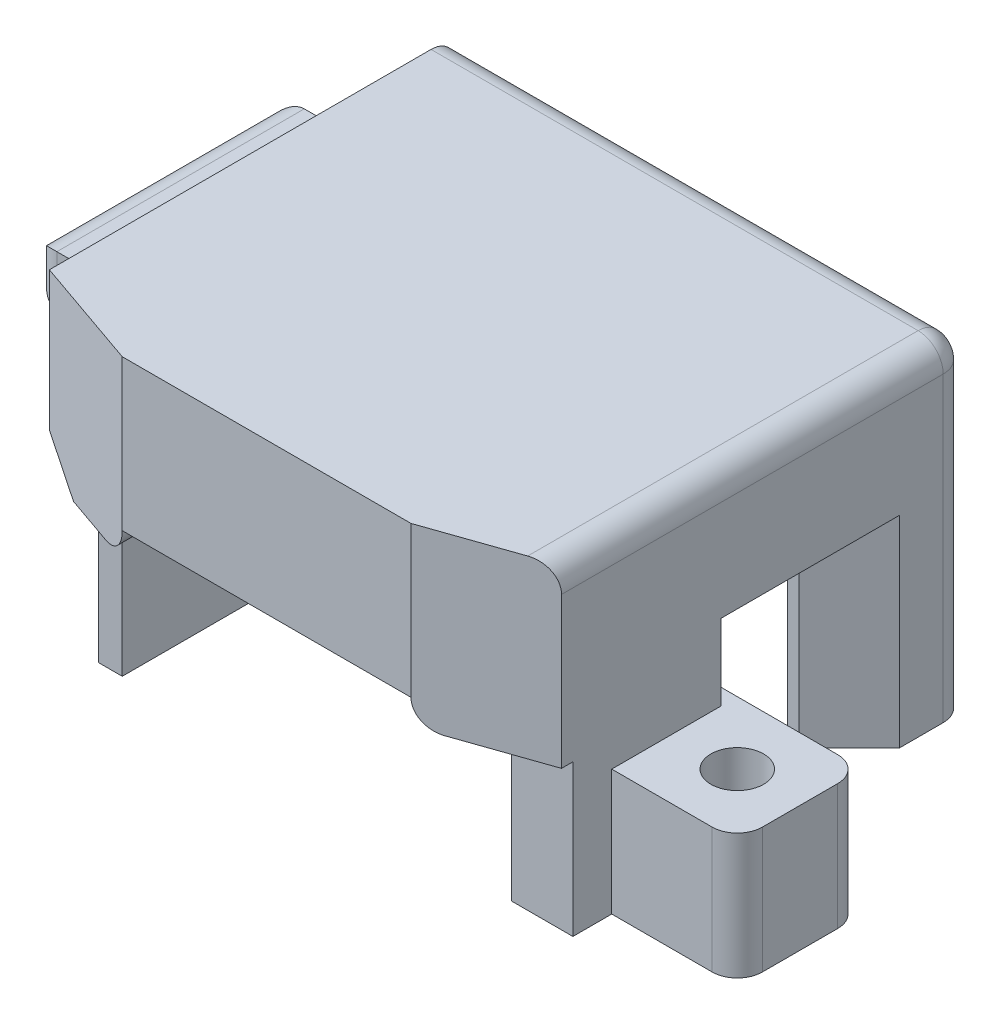
SolidWorks part; units mm, degrees
ref_plane "Front Plane" through (0, 0, 0) normal (0, 0, 1) x (1, 0, 0)
ref_plane "Top Plane" through (0, 0, 0) normal (0, 1, 0) x (1, 0, 0)
ref_plane "Right Plane" through (0, 0, 0) normal (1, 0, 0) x (0, 0, -1)
sketch "Sketch1" plane through (0, 0, 0) normal (0, 1, 0) x (1, 0, 0)
  line L1 (-22.86, -21.59) -> (22.86, -21.59)
  line L2 (-22.86, -21.59) -> (-22.86, 21.59)
  line L3 (-22.86, 21.59) -> (22.86, 21.59)
  line L4 (22.86, -21.59) -> (22.86, 21.59)
  line L5 (-22.86, -21.59) -> (22.86, 21.59) construction
  line L6 (-22.86, 21.59) -> (22.86, -21.59) construction
  point P0 (0, 0)
  dimension "D1" = 45.72
  dimension "D2" = 43.18
extrude "Boss-Extrude1" add sketch "Sketch1" along normal blind 31.75 contours L2 L1 L4 L3
sketch "Sketch2" plane through (0, 31.75, 0) normal (0, 1, 0) x (1, 0, 0)
  line L1 (-19.685, -18.415) -> (19.685, -18.415)
  line L2 (-19.685, -18.415) -> (-19.685, 18.415)
  line L3 (-19.685, 18.415) -> (19.685, 18.415)
  line L4 (19.685, -18.415) -> (19.685, 18.415)
  line L5 (-19.685, -18.415) -> (19.685, 18.415) construction
  line L6 (-19.685, 18.415) -> (19.685, -18.415) construction
  point P0 (0, 0)
  dimension "D1" = 39.37
  dimension "D2" = 36.83
extrude "Cut-Extrude3" cut sketch "Sketch2" against normal blind 25.4
sketch "Sketch3" plane through (0, 0, 21.59) normal (0, 0, 1) x (1, 0, 0)
  line L1 (-22.86, 31.75) -> (22.86, 31.75)
  line L2 (-22.86, 31.75) -> (-22.86, 0)
  line L3 (-22.86, 0) -> (22.86, 0)
  line L4 (22.86, 31.75) -> (22.86, 0)
extrude "Cut-Extrude5" cut sketch "Sketch3" against normal blind 3.175
sketch "Sketch6" plane through (0, 31.75, 0) normal (0, 1, 0) x (1, 0, 0)
  line L1 (-19.685, -18.415) -> (-22.86, -18.415)
  line L2 (-19.685, -18.415) -> (-19.685, 21.59)
  line L3 (-19.685, 21.59) -> (-22.86, 21.59)
  line L4 (-22.86, -18.415) -> (-22.86, 21.59)
  line L5 (19.685, -18.415) -> (22.86, -18.415)
  line L6 (19.685, -18.415) -> (19.685, 21.59)
  line L7 (19.685, 21.59) -> (22.86, 21.59)
  line L8 (22.86, -18.415) -> (22.86, 21.59)
  line L9 (-19.685, 18.415) -> (19.685, 18.415)
  line L10 (-19.685, 18.415) -> (-19.685, 21.59)
  line L11 (-19.685, 21.59) -> (19.685, 21.59)
  line L12 (19.685, 18.415) -> (19.685, 21.59)
  line M4 (-19.685, 18.415) -> (19.685, 18.415)
  line M5 (19.685, 18.415) -> (19.685, -18.415)
  line M6 (19.685, -18.415) -> (22.86, -18.415)
  line M7 (22.86, -18.415) -> (22.86, 21.59)
  line M8 (22.86, 21.59) -> (-22.86, 21.59)
extrude "Boss-Extrude4" add sketch "Sketch6" along normal up to vertex (38.1 mm away) contours L6 M5 M6 M7 M8 | L6 L2 M4 M8
sketch "Sketch7" plane through (0, 0, -18.415) normal (0, 0, 1) x (1, 0, 0)
  line L0 (19.685, 6.35) -> (19.685, 69.85) construction
  line L1 (-19.685, 69.85) -> (19.685, 69.85)
  line L2 (-19.685, 69.85) -> (-19.685, 44.6984)
  line L3 (-19.685, 44.6984) -> (19.685, 44.6984)
  line L4 (19.685, 69.85) -> (19.685, 44.6984)
extrude "Boss-Extrude5" add sketch "Sketch7" along normal up to vertex (36.83 mm away)
sketch "Sketch8" plane through (22.86, 0, 0) normal (1, 0, 0) x (0, 0, -1)
  line L1 (-18.415, 69.85) -> (21.59, 69.85)
  line L2 (-18.415, 69.85) -> (-18.415, 0)
  line L3 (-18.415, 0) -> (21.59, 0)
  line L4 (21.59, 69.85) -> (21.59, 0)
extrude "Boss-Extrude6" add sketch "Sketch8" along normal blind 6.35
sketch "Sketch9" plane through (-22.86, 0, 0) normal (-1, 0, 0) x (0, 0, 1)
  line L1 (18.415, 69.85) -> (-21.59, 69.85)
  line L2 (18.415, 69.85) -> (18.415, 0)
  line L3 (18.415, 0) -> (-21.59, 0)
  line L4 (-21.59, 69.85) -> (-21.59, 0)
extrude "Boss-Extrude7" add sketch "Sketch9" along normal blind 6.35
sketch "Sketch11" plane through (-29.21, 0, 0) normal (-1, 0, 0) x (0, 0, 1)
  line L0 (-1.5875, 69.85) -> (-1.5875, 58.2804)
  line L1 (18.415, 69.85) -> (-21.59, 69.85) construction
  line L2 (-1.5875, 58.2804) -> (-7.9375, 58.2804)
  line L4 (-7.9375, 58.2804) -> (4.7625, 58.2804)
  line L5 (-7.9375, 58.2804) -> (-7.9375, 44.3104)
  line L6 (-7.9375, 44.3104) -> (4.7625, 44.3104)
  line L7 (4.7625, 58.2804) -> (4.7625, 44.3104)
  dimension "D1" = 13.97
  dimension "D2" = 12.7
  dimension "D3" = 6.35
extrude "Cut-Extrude8" cut sketch "Sketch11" against normal blind 61.468 contours L7 L4 L2 L5 L6
sketch "Sketch12" plane through (-29.21, 0, 0) normal (-1, 0, 0) x (0, 0, 1)
  line L0 (4.7625, 58.2804) -> (4.7625, 69.85)
  line L1 (18.415, 69.85) -> (-21.59, 69.85) construction
sketch "Sketch13" plane through (0, 69.85, 0) normal (0, 1, 0) x (1, 0, 0)
  line L0 (-29.21, -4.7625) -> (29.21, -4.7625)
  line L1 (29.21, 21.59) -> (29.21, -18.415) construction
  line L3 (-29.21, -4.7625) -> (29.21, -4.7625)
  line L4 (-29.21, -4.7625) -> (-29.21, 21.59)
  line L5 (-29.21, 21.59) -> (29.21, 21.59)
  line L6 (29.21, -4.7625) -> (29.21, 21.59)
extrude "Boss-Extrude8" add sketch "Sketch13" along normal blind 16.002
sketch "Sketch14" plane through (0, 0, -21.59) normal (0, 0, -1) x (-1, 0, 0)
  line L0 (10.16, 85.852) -> (29.21, 85.852)
  line L1 (-29.21, 85.852) -> (29.21, 85.852) construction
  line L2 (0, 85.852) -> (-10.16, 85.852)
  line L3 (-10.16, 85.852) -> (-10.16, 73.1756)
  line L4 (-10.16, 73.1756) -> (-3.81, 73.1756)
  line L5 (-3.81, 73.1756) -> (10.16, 73.1756)
  line L6 (10.16, 73.1756) -> (10.16, 85.852)
  line L7 (10.16, 85.852) -> (0, 85.852)
  line L8 (-10.16, 73.1756) -> (10.16, 73.1756)
  line L9 (-29.21, 85.852) -> (-10.16, 85.852)
  line M3 (29.21, 85.852) -> (-29.21, 85.852)
extrude "Cut-Extrude9" cut sketch "Sketch14" against normal blind 16.51 contours L5 L6 L3 L4 M3
sketch "Sketch15" plane through (0, 0, 4.7625) normal (0, 0, 1) x (1, 0, 0)
  line L0 (-29.21, 85.852) -> (-18.8998, 85.852)
  line L1 (-29.21, 85.852) -> (29.21, 85.852) construction
  line L2 (29.21, 85.852) -> (19.0951, 85.852)
  line L3 (-29.21, 69.85) -> (29.21, 69.85) construction
  line L4 (-18.8998, 85.852) -> (19.0951, 85.852)
  line L5 (-18.8998, 85.852) -> (-18.8998, 69.85)
  line L6 (-18.8998, 69.85) -> (19.0951, 69.85)
  line L7 (19.0951, 85.852) -> (19.0951, 69.85)
extrude "Boss-Extrude9" add sketch "Sketch15" along normal blind 5.08 contours L5 L4 L7 L6
sketch "Sketch16" plane through (0, 0, 0) normal (0, -1, 0) x (1, 0, 0)
  line L1 (-29.21, 18.415) -> (29.21, 18.415)
  line L2 (-29.21, 18.415) -> (-29.21, -21.59)
  line L3 (-29.21, -21.59) -> (29.21, -21.59)
  line L4 (29.21, 18.415) -> (29.21, -21.59)
extrude "Cut-Extrude11" cut sketch "Sketch16" against normal blind 38.1
sketch "Sketch17" plane through (0, 44.3104, 0) normal (0, 1, 0) x (1, 0, 0)
  line L1 (29.21, 7.9375) -> (19.685, 7.9375)
  line L2 (29.21, 7.9375) -> (29.21, -4.7625)
  line L3 (29.21, -4.7625) -> (19.685, -4.7625)
  line L4 (19.685, 7.9375) -> (19.685, -4.7625)
extrude "Boss-Extrude10" add sketch "Sketch17" along normal up to vertex (13.97 mm away)
sketch "Sketch18" plane through (0, 44.3104, 0) normal (0, 1, 0) x (1, 0, 0)
  line L1 (-29.21, 7.9375) -> (-19.685, 7.9375)
  line L2 (-29.21, 7.9375) -> (-29.21, -4.7625)
  line L3 (-29.21, -4.7625) -> (-19.685, -4.7625)
  line L4 (-19.685, 7.9375) -> (-19.685, -4.7625)
extrude "Boss-Extrude11" add sketch "Sketch18" along normal up to vertex (13.97 mm away)
sketch "Sketch19" plane through (0, 0, 18.415) normal (0, 0, 1) x (1, 0, 0)
  line L6 (19.685, 44.6984) -> (-19.685, 44.6984)
  line L7 (19.685, 44.6984) -> (19.685, 48.5084)
  line L8 (19.685, 48.5084) -> (-19.685, 48.5084)
  line L9 (-19.685, 44.6984) -> (-19.685, 48.5084)
  dimension "D1" = 3.81
extrude "Boss-Extrude14" add sketch "Sketch19" along normal blind 5.08
sketch "Sketch21" plane through (0, 44.6984, 0) normal (0, -1, 0) x (1, 0, 0)
  line L0 (-19.685, 18.415) -> (-19.685, 23.495)
  line L1 (-19.685, 23.495) -> (-14.605, 23.495)
  line L2 (-19.685, 23.495) -> (19.685, 23.495) construction
  line L3 (-14.605, 23.495) -> (-19.685, 18.415)
  line L4 (19.685, 18.415) -> (19.685, 23.495)
  line L5 (19.685, 23.495) -> (14.605, 23.495)
  line L6 (14.605, 23.495) -> (19.685, 18.415)
  dimension "D1" = 5.08
  dimension "D2" = 5.08
extrude "Cut-Extrude12" cut sketch "Sketch21" against normal up to vertex (3.81 mm away) contours L6 L4 L5 | L3 L0 L1
sketch "Sketch34" plane through (0, 44.6984, 0) normal (0, -1, 0) x (-1, 0, 0)
  line L0 (14.605, -23.495) -> (19.685, -18.415)
  line L1 (19.685, -18.415) -> (14.605, -18.415)
  line L2 (14.605, -18.415) -> (14.605, -23.495)
sketch "Sketch35" plane through (0, 0, 18.415) normal (0, 0, 1) x (1, 0, 0)
  line L0 (19.685, 44.6984) -> (29.21, 44.6984)
  line L1 (29.21, 69.85) -> (29.21, 38.1) construction
  line L2 (-19.685, 44.6984) -> (-29.21, 44.6984)
  line L3 (-29.21, 38.1) -> (-29.21, 69.85) construction
sketch "Sketch36" plane through (0, 44.6984, 0) normal (0, -1, 0) x (1, 0, 0)
  line L0 (-14.605, 23.495) -> (-29.21, 18.415)
  line L1 (-19.685, 18.415) -> (-29.21, 18.415) construction
  line L2 (-29.21, 18.415) -> (-14.605, 18.415)
  line L3 (-14.605, 18.415) -> (-14.605, 23.495)
  line L4 (14.605, 23.495) -> (29.21, 18.415)
  line L5 (29.21, 18.415) -> (14.605, 18.415)
  line L6 (14.605, 18.415) -> (14.605, 23.495)
extrude "Boss-Extrude22" add sketch "Sketch36" against normal up to vertex (3.81 mm away) up to point (-14.605, 48.5084, 23.495)
sketch "Sketch37" plane through (0, 48.5084, 0) normal (0, 1, 0) x (1, 0, 0)
  line L0 (-29.21, -18.415) -> (-14.605, -23.495)
  line L1 (-14.605, -23.495) -> (14.605, -23.495)
  line L2 (14.605, -23.495) -> (29.21, -18.415)
  line L3 (29.21, -18.415) -> (-29.21, -18.415)
extrude "Boss-Extrude23" add sketch "Sketch37" along normal up to vertex
sketch "Sketch39" plane through (0, 44.6984, 0) normal (0, -1, 0) x (1, 0, 0)
  line L0 (-29.21, 18.415) -> (-14.605, 23.495)
  line L1 (-14.605, 23.495) -> (14.605, 23.495)
  line L2 (14.605, 23.495) -> (29.21, 18.415)
  line L3 (29.21, 18.415) -> (-29.21, 18.415)
extrude "Boss-Extrude24" add sketch "Sketch39" along normal up to vertex (6.5984 mm away)
sketch "Sketch40" plane through (0, 38.1, 0) normal (0, -1, 0) x (-1, 0, 0)
  line L0 (-29.21, 21.59) -> (29.21, 21.59)
  line L1 (29.21, 21.59) -> (29.21, -18.415)
  line L2 (29.21, -18.415) -> (14.605, -23.495)
  line L3 (14.605, -23.495) -> (-14.605, -23.495)
  line L4 (-14.605, -23.495) -> (-29.21, -18.415)
  line L5 (-29.21, -18.415) -> (-29.21, 21.59)
  line L6 (-19.685, 18.415) -> (-19.685, -18.415)
  line L7 (-19.685, -18.415) -> (19.685, -18.415)
  line L8 (19.685, -18.415) -> (19.685, 18.415)
  line L9 (19.685, 18.415) -> (-19.685, 18.415)
  line L10 (8.618, -12.0581) -> (8.725, -12.0414)
  line M7 (19.685, -18.415) -> (-19.685, -18.415)
  line M8 (-19.685, -18.415) -> (-19.685, 18.415)
  line M9 (-19.685, 18.415) -> (19.685, 18.415)
  line M10 (19.685, 18.415) -> (19.685, -18.415)
  line M11 (-29.21, 21.59) -> (-29.21, -18.415)
  line M12 (-29.21, -18.415) -> (-14.605, -23.495)
  line M13 (-14.605, -23.495) -> (14.605, -23.495)
  line M14 (14.605, -23.495) -> (29.21, -18.415)
  line M15 (29.21, -18.415) -> (29.21, 21.59)
  line M16 (29.21, 21.59) -> (-29.21, 21.59)
extrude "Boss-Extrude25" add sketch "Sketch40" along normal blind 4.826 contours M16 M11 M12 M13 M14 M15 M10 M7 M8 M9
sketch "Sketch42" plane through (0, 0, 9.8425) normal (0, 0, 1) x (1, 0, 0)
  line L1 (-18.8998, 85.852) -> (19.0951, 85.852)
  line L2 (-18.8998, 85.852) -> (-18.8998, 69.85)
  line L3 (-18.8998, 69.85) -> (19.0951, 69.85)
  line L4 (19.0951, 85.852) -> (19.0951, 69.85)
extrude "Boss-Extrude26" add sketch "Sketch42" along normal blind 3.302
sketch "Sketch43" plane through (0, 0, 4.7625) normal (0, 0, -1) x (-1, 0, 0)
  line L1 (19.685, 58.2804) -> (-19.685, 58.2804)
  line L2 (19.685, 58.2804) -> (19.685, 44.6984)
  line L3 (19.685, 44.6984) -> (-19.685, 44.6984)
  line L4 (-19.685, 58.2804) -> (-19.685, 44.6984)
extrude "Cut-Extrude13" cut sketch "Sketch43" against normal blind 6.35
sketch "Sketch45" plane through (0, 0, -7.9375) normal (0, 0, 1) x (1, 0, 0)
  line L1 (-19.685, 58.2804) -> (19.685, 58.2804)
  line L2 (-19.685, 58.2804) -> (-19.685, 44.6984)
  line L3 (-19.685, 44.6984) -> (19.685, 44.6984)
  line L4 (19.685, 58.2804) -> (19.685, 44.6984)
extrude "Boss-Extrude27" add sketch "Sketch45" along normal up to vertex
sketch "Sketch46" plane through (-29.21, 0, 0) normal (-1, 0, 0) x (0, 0, 1)
  line L0 (-21.59, 85.852) -> (-21.59, 33.274)
  line L1 (-21.59, 33.274) -> (18.415, 33.274)
  line L2 (18.415, 33.274) -> (18.415, 69.85)
  line L3 (18.415, 69.85) -> (13.1445, 69.85)
  line L4 (13.1445, 69.85) -> (13.1445, 85.852)
  line L5 (13.1445, 85.852) -> (-21.59, 85.852)
extrude "Cut-Extrude15" cut sketch "Sketch46" against normal blind 3.302
sketch "Sketch47" plane through (29.21, 0, 0) normal (1, 0, 0) x (0, 0, -1)
  line L0 (-4.7625, 85.852) -> (-4.7625, 69.85)
  line L1 (-4.7625, 69.85) -> (-18.415, 69.85)
  line L2 (-18.415, 69.85) -> (-18.415, 33.274)
  line L3 (-18.415, 33.274) -> (21.59, 33.274)
  line L4 (21.59, 33.274) -> (21.59, 85.852)
  line L5 (21.59, 33.274) -> (21.59, 85.852) construction
  line L6 (21.59, 85.852) -> (-4.7625, 85.852)
extrude "Cut-Extrude16" cut sketch "Sketch47" against normal blind 3.302
sketch "Sketch48" plane through (0, 0, 18.415) normal (0, 0, -1) x (-1, 0, 0)
  line L1 (-29.21, 69.85) -> (-25.908, 69.85)
  line L2 (-29.21, 69.85) -> (-29.21, 33.274)
  line L3 (-29.21, 33.274) -> (-25.908, 33.274)
  line L4 (-25.908, 69.85) -> (-25.908, 33.274)
extrude "Cut-Extrude17" cut sketch "Sketch48" against normal blind 3.302
sketch "Sketch49" plane through (0, 0, 18.415) normal (0, 0, -1) x (-1, 0, 0)
  line L1 (29.21, 69.85) -> (25.908, 69.85)
  line L2 (29.21, 69.85) -> (29.21, 33.274)
  line L3 (29.21, 33.274) -> (25.908, 33.274)
  line L4 (25.908, 69.85) -> (25.908, 33.274)
extrude "Cut-Extrude18" cut sketch "Sketch49" against normal blind 3.302
sketch "Sketch50" plane through (0, 85.852, 0) normal (0, 1, 0) x (1, 0, 0)
  line L1 (-25.908, 21.59) -> (37.3188, 21.59)
  line L2 (-25.908, 21.59) -> (-25.908, -24.3963)
  line L3 (-25.908, -24.3963) -> (37.3188, -24.3963)
  line L4 (37.3188, 21.59) -> (37.3188, -24.3963)
extrude "Cut-Extrude19" cut sketch "Sketch50" against normal up to vertex (16.002 mm away)
sketch "Sketch51" plane through (0, 69.85, 0) normal (0, 1, 0) x (1, 0, 0)
  line L1 (-25.908, 21.59) -> (29.0656, 21.59)
  line L2 (-25.908, 21.59) -> (-25.908, -24.9944)
  line L3 (-25.908, -24.9944) -> (29.0656, -24.9944)
  line L4 (29.0656, 21.59) -> (29.0656, -24.9944)
extrude "Cut-Extrude20" cut sketch "Sketch51" against normal blind 18.796
sketch "Sketch52" plane through (0, 33.274, 0) normal (0, -1, 0) x (-1, 0, 0)
  line L0 (-25.908, -19.5635) -> (-25.908, 21.59) construction
  line L1 (-19.685, -18.415) -> (-25.908, -18.415)
  line L2 (-19.685, -18.415) -> (-19.685, 1.6404)
  line L3 (-19.685, 1.6404) -> (-25.908, 1.6404)
  line L4 (-25.908, -18.415) -> (-25.908, 1.6404)
  line L6 (-25.908, 9.525) -> (-19.685, 9.525)
  line L7 (-25.908, 9.525) -> (-25.908, 18.415)
  line L8 (-25.908, 18.415) -> (-19.685, 18.415)
  line L9 (-19.685, 9.525) -> (-19.685, 18.415)
  line L10 (19.685, -18.415) -> (25.908, -18.415)
  line L11 (19.685, -18.415) -> (19.685, 21.59)
  line L12 (19.685, 21.59) -> (25.908, 21.59)
  line L13 (25.908, -18.415) -> (25.908, 21.59)
  line L14 (-25.908, 21.59) -> (19.685, 21.59)
  line L15 (-25.908, 21.59) -> (-25.908, 18.415)
  line L16 (-25.908, 18.415) -> (19.685, 18.415)
  line L17 (19.685, 21.59) -> (19.685, 18.415)
  line M2 (25.908, -19.5635) -> (25.908, 21.59)
  line M3 (25.908, 21.59) -> (-25.908, 21.59)
  line M4 (-25.908, 21.59) -> (-25.908, -19.5635)
  line M7 (19.685, 18.415) -> (19.685, -18.415)
  line M9 (-19.685, -18.415) -> (-19.685, 18.415)
  line M10 (-19.685, 18.415) -> (19.685, 18.415)
  dimension "D1" = 8.89
extrude "Boss-Extrude28" add sketch "Sketch52" along normal blind 15.3035 contours L3 L1 M9 M4 | L8 L6 M4 M9 | L11 L8 M10 M3 M4 | L11 L10 M7 M2 M3
sketch "Sketch53" plane through (25.908, 0, 0) normal (1, 0, 0) x (0, 0, -1)
  line L1 (-18.415, 17.9705) -> (-5.715, 17.9705)
  line L2 (-18.415, 17.9705) -> (-18.415, 21.7805)
  line L3 (-18.415, 21.7805) -> (-5.715, 21.7805)
  line L4 (-5.715, 17.9705) -> (-5.715, 21.7805)
  dimension "D1" = 12.7
  dimension "D2" = 3.81
sketch "Sketch54" plane through (-25.908, 0, 0) normal (-1, 0, 0) x (0, 0, 1)
  line L1 (18.415, 17.9705) -> (5.715, 17.9705)
  line L2 (18.415, 17.9705) -> (18.415, 21.7805)
  line L3 (18.415, 21.7805) -> (5.715, 21.7805)
  line L4 (5.715, 17.9705) -> (5.715, 21.7805)
extrude "Boss-Extrude29" add sketch "Sketch53" along normal blind 10.16
extrude "Boss-Extrude30" add sketch "Sketch54" along normal blind 10.16
sketch "Sketch55" plane through (0, 21.7805, 0) normal (0, 1, 0) x (1, 0, 0)
  line L0 (36.068, -18.415) -> (25.908, -18.415) construction
  line L1 (36.068, -5.715) -> (36.068, -18.415) construction
  line L2 (30.988, -18.415) -> (36.068, -18.415)
  line L3 (36.068, -18.415) -> (36.068, -12.065)
  arc A0 (30.988, -18.415) -> (36.068, -12.065) centre (30.353, -12.7) ccw
  line M2 (25.908, -18.415) -> (36.068, -18.415)
  line M3 (36.068, -18.415) -> (36.068, -5.715)
extrude "Cut-Extrude21" cut sketch "Sketch55" against normal blind 12.7 contours A0 M2 M3
sketch "Sketch56" plane through (0, 21.7805, 0) normal (0, 1, 0) x (1, 0, 0)
  line L0 (-36.068, -18.415) -> (-25.908, -18.415) construction
  line L1 (-36.068, -18.415) -> (-36.068, -5.715) construction
  line L2 (-30.988, -18.415) -> (-36.068, -18.415)
  line L3 (-36.068, -18.415) -> (-36.068, -12.065)
  arc A0 (-30.988, -18.415) -> (-36.068, -12.065) centre (-30.353, -12.7) cw
  line M4 (-36.068, -18.415) -> (-25.908, -18.415)
extrude "Cut-Extrude22" cut sketch "Sketch56" against normal blind 12.7 contours A0 L3 M4
sketch "Sketch60" plane through (0, 21.7805, 0) normal (0, 1, 0) x (1, 0, 0)
  circle A0 centre (30.353, -12.7) radius 2.667
  circle A1 centre (-30.353, -12.7) radius 2.667
extrude "Cut-Extrude25" cut sketch "Sketch60" against normal blind 10.16
sketch "Sketch62" plane through (0, 33.274, 0) normal (0, -1, 0) x (1, 0, 0)
  line L0 (-19.685, 18.415) -> (19.685, 18.415) construction
  line L1 (-14.605, 23.495) -> (14.605, 23.495)
  line L2 (-14.605, 23.495) -> (-14.605, 18.415)
  line L3 (-14.605, 18.415) -> (14.605, 18.415)
  line L4 (14.605, 23.495) -> (14.605, 18.415)
extrude "Cut-Extrude27" cut sketch "Sketch62" against normal blind 2.54
sketch "Sketch63" plane through (0, 0, -18.415) normal (0, 0, 1) x (1, 0, 0)
  line L0 (19.685, 17.9705) -> (-19.685, 17.9705) construction
  line L1 (-12.7, -1.0795) -> (12.7, -1.0795)
  line L2 (-12.7, -1.0795) -> (-12.7, 37.0205)
  line L3 (-12.7, 37.0205) -> (12.7, 37.0205)
  line L4 (12.7, -1.0795) -> (12.7, 37.0205)
  line L5 (-12.7, -1.0795) -> (12.7, 37.0205) construction
  line L6 (-12.7, 37.0205) -> (12.7, -1.0795) construction
  point P0 (0, 17.9705)
  dimension "D1" = 25.4
  dimension "D2" = 38.1
extrude "Cut-Extrude28" cut sketch "Sketch63" against normal up to vertex (3.175 mm away)
sketch "Sketch64" plane through (0, 17.9705, 0) normal (0, -1, 0) x (1, 0, 0)
  line L1 (-25.908, 5.715) -> (-38.0106, 5.715)
  line L2 (-25.908, 5.715) -> (-25.908, 21.3748)
  line L3 (-25.908, 21.3748) -> (-38.0106, 21.3748)
  line L4 (-38.0106, 5.715) -> (-38.0106, 21.3748)
  line L5 (25.908, 5.715) -> (37.8437, 5.715)
  line L6 (25.908, 5.715) -> (25.908, 20.4269)
  line L7 (25.908, 20.4269) -> (37.8437, 20.4269)
  line L8 (37.8437, 5.715) -> (37.8437, 20.4269)
extrude "Cut-Extrude29" cut sketch "Sketch64" against normal up to vertex (3.81 mm away) up to point (-36.068, 21.7805, 13.335)
sketch "Sketch65" plane through (0, 17.9705, 0) normal (0, -1, 0) x (1, 0, 0)
  line L0 (25.908, 14.4835) -> (25.908, 1.7835)
  line L2 (25.908, 19.5635) -> (25.908, 14.4835)
  line L3 (25.908, -1.6404) -> (25.908, 18.415) construction
  line L5 (-13.208, -21.59) -> (-25.908, -21.59)
  line L6 (-13.208, -21.59) -> (-13.208, -34.29)
  line L7 (-13.208, -34.29) -> (-25.908, -34.29)
  line L8 (-25.908, -21.59) -> (-25.908, -34.29)
  line L9 (25.908, 14.4835) -> (38.608, 14.4835)
  line L10 (25.908, 14.4835) -> (25.908, 1.7835)
  line L11 (25.908, 1.7835) -> (38.608, 1.7835)
  line L12 (38.608, 14.4835) -> (38.608, 1.7835)
  circle A4 centre (-19.558, -27.94) radius 2.667
  circle A5 centre (32.258, 8.1335) radius 2.667
  point P2 (-25.908, -27.94)
  point P3 (-19.558, -34.29)
  point P20 (38.608, 8.1335)
  point P21 (32.258, 14.4835)
  line M8 (-25.908, 18.415) -> (-25.908, -21.59)
  dimension "D7" = 5.334
  dimension "D2" = 5.08
  dimension "D3" = 12.7
  dimension "D4" = 12.7
  dimension "D5" = 12.7
  dimension "D6" = 12.7
extrude "Boss-Extrude31" add sketch "Sketch65" against normal blind 12.7 contours L5 L8 L7 A5 M8 | L12 L9 L10 L11 A4
sketch "Sketch66" plane through (-19.685, 0, 0) normal (1, 0, 0) x (0, 0, -1)
  line L0 (18.415, 17.9705) -> (18.415, 44.6984) construction
  line L1 (4.953, 17.9705) -> (11.303, 17.9705)
  line L2 (4.953, 17.9705) -> (4.953, 31.9405)
  line L3 (4.953, 31.9405) -> (11.303, 31.9405)
  line L4 (11.303, 17.9705) -> (11.303, 31.9405)
  dimension "D1" = 7.112
  dimension "D2" = 13.97
  dimension "D3" = 6.35
extrude "Cut-Extrude30" cut sketch "Sketch66" against normal through all
sketch "Sketch68" plane through (0, 0, 18.415) normal (0, 0, 1) x (1, 0, 0)
  line L1 (-25.908, 17.9705) -> (-22.098, 17.9705)
  line L2 (-25.908, 17.9705) -> (-25.908, 31.9405)
  line L3 (-25.908, 31.9405) -> (-22.098, 31.9405)
  line L4 (-22.098, 17.9705) -> (-22.098, 31.9405)
  line L5 (-25.908, 31.9405) -> (-19.685, 31.9405) construction
extrude "Cut-Extrude31" cut sketch "Sketch68" against normal up to surface (29.718 mm away) up to face at (-22.7965, 24.9555, -11.303)
chamfer "Chamfer1" distance 5.08 angle 45 9 edges at (25.908, 33.274, -5.5827) (25.908, 25.6222, -1.6404) (-25.908, 33.274, 18.9893) (25.908, 25.6222, -9.525) (25.908, 24.3205, 1.7835) (-25.908, 31.9405, 3.556) (-25.908, 32.6072, 18.415) (-22.098, 31.9405, 6.731) (-24.003, 31.9405, 18.415)
sketch "Sketch67" plane through (-25.908, 0, 0) normal (-1, 0, 0) x (0, 0, 1)
  line L0 (-11.303, 17.9705) -> (-11.303, 37.0205)
  line L3 (-11.303, 37.0205) -> (8.6466, 37.0205)
  line L4 (8.6466, 37.0205) -> (8.6466, 42.1005)
  line L5 (8.6466, 42.1005) -> (-9.398, 42.1005)
  line L6 (-9.398, 42.1005) -> (-16.383, 42.1005)
  line L8 (-16.383, 42.1005) -> (-16.383, 17.9705)
  line L9 (-11.303, 17.9705) -> (-34.29, 17.9705) construction
  line L10 (-16.383, 17.9705) -> (-11.303, 17.9705)
  point P2 (0, 0)
  point P3 (-60.8719, 38.7204)
  dimension "D1" = 25.0296
  dimension "D2" = 5.08
  dimension "D3" = 5.08
extrude "Boss-Extrude32" add sketch "Sketch67" along normal blind 12.7
fillet "Fillet8" radius 2.54 1 edges at (14.605, 33.274, 20.955)
fillet "Fillet9" radius 2.54 1 edges at (-14.605, 33.274, 20.955)
fillet "Fillet13" radius 2.54 3 edges at (-12.7, 27.4955, -21.59) (12.7, 27.4955, -21.59) (0, 37.0205, -21.59)
fillet "Fillet14" radius 2.54 4 edges at (38.608, 24.3205, 14.4835) (38.608, 24.3205, 1.7835) (-25.908, 24.3205, -34.29) (-13.208, 24.3205, -34.29)
fillet "Fillet1" radius 2.54 1 edges at (25.908, 51.054, -1.0132)
fillet "Fillet2" radius 2.54 3 edges at (25.908, 33.2422, -21.59) (-1.27, 51.054, -21.59) (25.1641, 50.3101, -21.59)
fillet "Fillet17" radius 2.54 5 edges at (-38.608, 39.5605, 8.6466) (-38.608, 37.0205, -1.3282) (-38.608, 42.1005, -3.8682) (-38.608, 30.0355, -16.383) (-38.608, 27.4955, -11.303)
chamfer "Chamfer2" distance 1.27 angle 45 1 edges at (-22.098, 25.5905, -4.953)
